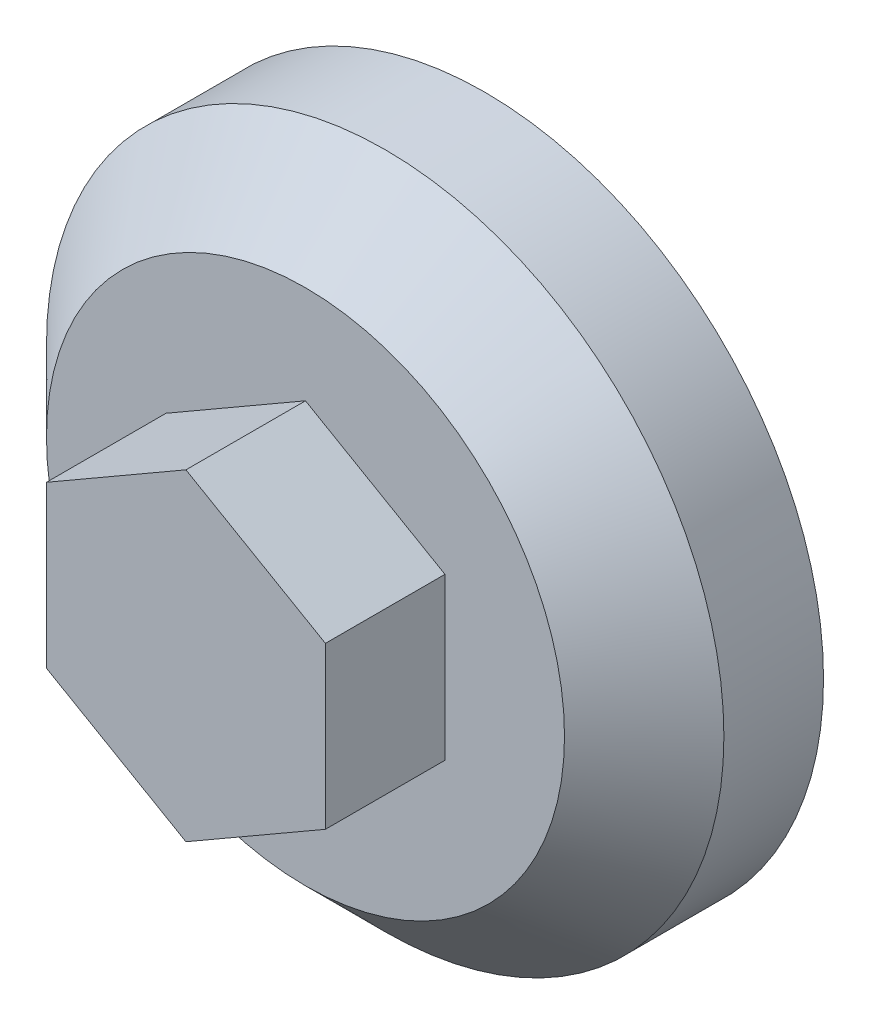
SolidWorks part; units mm, degrees
material "POM Acetal Copolymer"
ref_plane "Front Plane" through (0, 0, 0) normal (0, 0, 1) x (1, 0, 0)
ref_plane "Top Plane" through (0, 0, 0) normal (0, 1, 0) x (1, 0, 0)
ref_plane "Right Plane" through (0, 0, 0) normal (1, 0, 0) x (0, 0, -1)
sketch "Revolve profile 1" plane through (0, 0, 0) normal (0, 1, 0) x (1, 0, 0)
  line L0 (0, 0) -> (17, 0)
  line L1 (17, 0) -> (17, -5)
  line L2 (17, -5) -> (13, -9)
  line L3 (13, -9) -> (0, -9)
  line L4 (0, -9) -> (0, 0)
  line L5 (0, 5) -> (0, -14) construction
  dimension "D1" = 4
  dimension "D2" = 17
  dimension "D3" = 5
  dimension "D4" = 9
revolve "Revolve 1" add sketch "Revolve profile 1" angle 360 about L5
sketch "Extrude sketch 1" plane through (0, 0, 0) normal (0, 0, 1) x (1, 0, 0)
  line L0 (7, 4.0415) -> (0, 8.0829)
  line L1 (0, 8.0829) -> (-7, 4.0415)
  line L2 (-7, 4.0415) -> (-7, -4.0415)
  line L3 (-7, -4.0415) -> (0, -8.0829)
  line L4 (0, -8.0829) -> (7, -4.0415)
  line L5 (7, -4.0415) -> (7, 4.0415)
  dimension "D1" = 7
  dimension "D2" = 4.0415
extrude "Extrude 1" add sketch "Extrude sketch 1" along normal blind 6 from offset 9 separate body
combine bodies "Combine (weld / assembly of features)" operation type add bodies to combine 101 102
